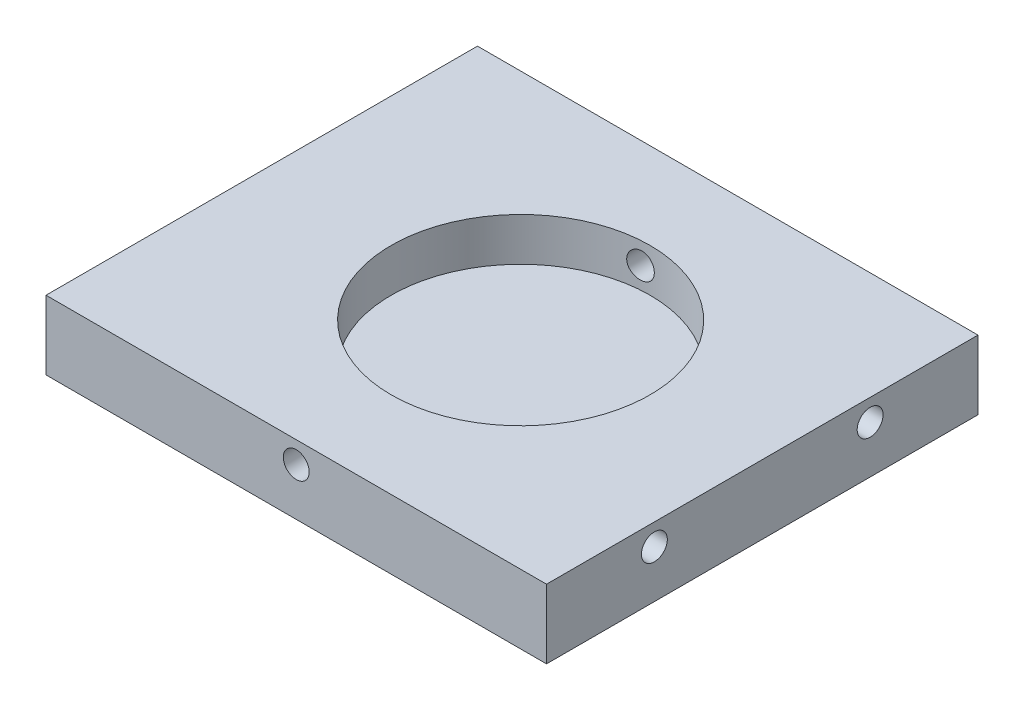
SolidWorks part; units mm, degrees
ref_plane "Plan de face" through (0, 0, 0) normal (0, 0, 1) x (1, 0, 0)
ref_plane "Plan de dessus" through (0, 0, 0) normal (0, 1, 0) x (1, 0, 0)
ref_plane "Plan de droite" through (0, 0, 0) normal (1, 0, 0) x (0, 0, -1)
sketch "Esquisse1" plane through (0, 0, 0) normal (0, 0, 1) x (1, 0, 0)
  line L0 (-5.5, -49) -> (52.5, -49) construction
  line L5 (-5.5, -45) -> (52.5, -45)
  line L6 (-5.5, -45) -> (-5.5, -53)
  line L7 (-5.5, -53) -> (52.5, -53)
  line L8 (52.5, -45) -> (52.5, -53)
  line L9 (23.5, -45) -> (23.5, -53) construction
  dimension "D1" = 8
  dimension "D2" = 58
extrude "Boss.-Extru.1" add sketch "Esquisse1" along normal blind 50 contours L5 | L7 L8 L5 L6
sketch "Esquisse2" plane through (0, -45, 0) normal (0, 1, 0) x (-1, 0, 0)
  line L0 (5.5, 50) -> (-52.5, 50) construction
  line L7 (-52.5, 50) -> (-52.5, 0) construction
  circle A0 centre (-24.5, 25) radius 15
  dimension "D10" = 28
  dimension "D11" = 25
extrude "Enlèv. mat.-Extru.1" cut sketch "Esquisse2" against normal blind 5
sketch "Esquisse3" plane through (-5.5, 0, 0) normal (-1, 0, 0) x (0, 0, 1)
  line L0 (50, -53) -> (0, -53) construction
  line L1 (0, -45) -> (0, -53) construction
  line L2 (50, -45) -> (50, -53) construction
  circle A0 centre (12.5, -47.5) radius 1.5
  circle A1 centre (37.5, -47.5) radius 1.5
  dimension "D1" = 5.5
  dimension "D2" = 5.5
  dimension "D3" = 12.5
  dimension "D4" = 12.5
extrude "Enlèv. mat.-Extru.2" cut sketch "Esquisse3" against normal blind 10
sketch "Esquisse4" plane through (52.5, 0, 0) normal (1, 0, 0) x (0, 0, -1)
  line L0 (-50, -53) -> (0, -53) construction
  line L1 (-50, -45) -> (-50, -53) construction
  line L2 (0, -45) -> (0, -53) construction
  circle A0 centre (-37.5, -47.5) radius 1.5
  circle A1 centre (-12.5, -47.5) radius 1.5
  dimension "D1" = 5.5
  dimension "D2" = 5.5
  dimension "D3" = 12.5
  dimension "D4" = 12.5
extrude "Enlèv. mat.-Extru.3" cut sketch "Esquisse4" against normal blind 10
sketch "Esquisse5" plane through (0, 0, 0) normal (0, 0, -1) x (-1, 0, 0)
  line L0 (5.5, -45) -> (-52.5, -45) construction
  line L1 (-52.5, -45) -> (-52.5, -53) construction
  circle A0 centre (-23.5, -47.5) radius 1.5
  dimension "D1" = 2.5
  dimension "D2" = 29
extrude "Enlèv. mat.-Extru.4" cut sketch "Esquisse5" against normal through all
